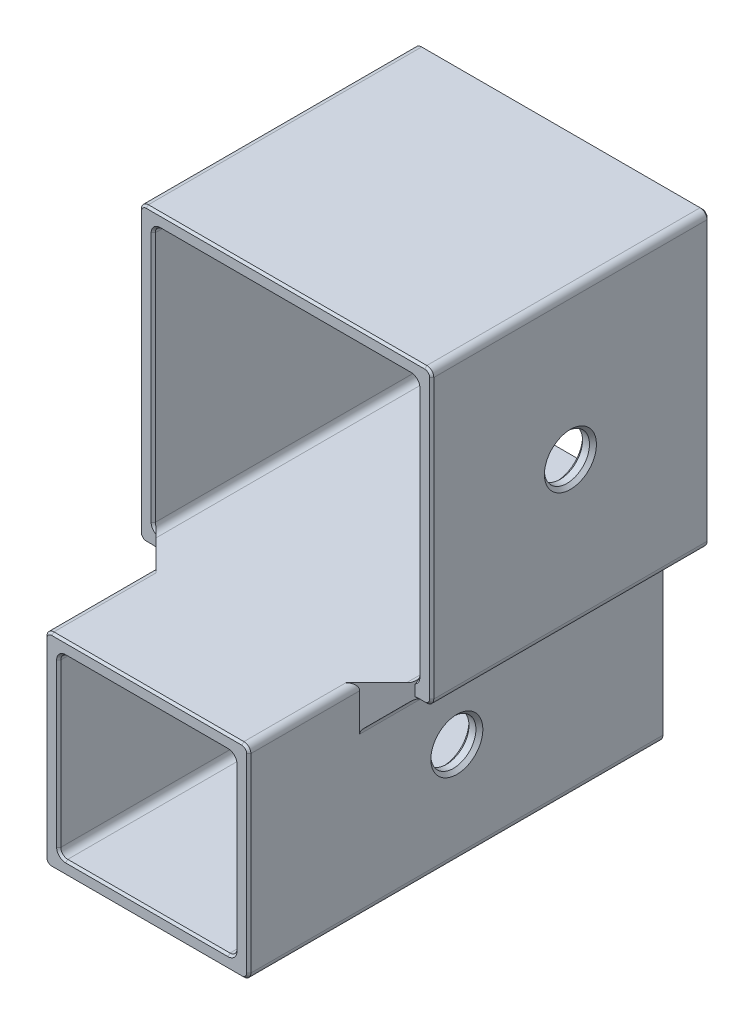
SolidWorks part; units mm, degrees
ref_plane "Front Plane" through (0, 0, 0) normal (0, 0, 1) x (1, 0, 0)
ref_plane "Top Plane" through (0, 0, 0) normal (0, 1, 0) x (1, 0, 0)
ref_plane "Right Plane" through (0, 0, 0) normal (1, 0, 0) x (0, 0, -1)
sketch "Sketch1" plane through (0, 0, 0) normal (0, 0, 1) x (1, 0, 0)
  line L0 (-21.075, -21.075) -> (-21.075, 21.075)
  line L1 (19.075, -19.075) -> (-19.075, -19.075)
  line L2 (19.075, -19.075) -> (19.075, 19.075)
  line L3 (19.075, 19.075) -> (-19.075, 19.075)
  line L4 (-19.075, -19.075) -> (-19.075, 19.075)
  line L5 (19.075, -19.075) -> (-19.075, 19.075) construction
  line L6 (19.075, 19.075) -> (-19.075, -19.075) construction
  line L7 (21.075, 21.075) -> (-21.075, 21.075)
  line L8 (21.075, -21.075) -> (21.075, 21.075)
  line L9 (21.075, -21.075) -> (-21.075, -21.075)
  point P0 (0, 0)
  dimension "D1" = 38.15
  dimension "D2" = 2
extrude "Boss-Extrude1" add sketch "Sketch1" along normal blind 40
sketch "Sketch3" plane through (0, 0, 40) normal (0, 0, 1) x (1, 0, 0)
  line L1 (12.7, -46.475) -> (-12.7, -46.475)
  line L2 (12.7, -46.475) -> (12.7, -21.075)
  line L3 (12.7, -21.075) -> (-12.7, -21.075)
  line L4 (-12.7, -46.475) -> (-12.7, -21.075)
  line L5 (12.7, -46.475) -> (-12.7, -21.075) construction
  line L6 (12.7, -21.075) -> (-12.7, -46.475) construction
  line L7 (-21.075, -21.075) -> (21.075, -21.075) construction
  line L8 (-14.7, -48.475) -> (-14.7, -19.075)
  line L9 (14.7, -19.075) -> (-14.7, -19.075)
  line L10 (14.7, -48.475) -> (14.7, -19.075)
  line L11 (14.7, -48.475) -> (-14.7, -48.475)
  point P0 (0, -33.775)
  point P7 (0, 0)
  dimension "D1" = 25.4
  dimension "D2" = 2
extrude "Boss-Extrude2" add sketch "Sketch3" along normal blind 20 and the other way up to surface
chamfer "Chamfer1" distance 4 angle 45 4 edges at (14.7, -20.075, 40) (-14.7, -20.075, 40) (14.7, -21.075, 20) (-14.7, -21.075, 20)
fillet "Fillet1" radius 1 20 edges at (-18.7, -21.075, 20) (-14.7, -25.075, 22) (14.7, -25.075, 22) (18.7, -21.075, 20) (14.7, -48.475, 30) (-14.7, -48.475, 30) (-21.075, -21.075, 20) (21.075, -21.075, 20) (21.075, 21.075, 20) (-21.075, 21.075, 20) (12.7, -46.475, 30) (12.7, -21.075, 30) (-12.7, -21.075, 30) (-12.7, -46.475, 30) (-19.075, -19.075, 20) (-19.075, 19.075, 20) (19.075, 19.075, 20) (19.075, -19.075, 20) (14.7, -19.075, 52) (-14.7, -19.075, 52)
chamfer "Chamfer2" distance 0.3 angle 45 70 edges at (-19.5946, -21.075, 40) (-16.7, -23.075, 0) (16.7, -23.075, 0) (19.5946, -21.075, 40) (19.5946, -21.075, 0) (0, -48.475, 0) (19.075, 0, 0) (0, 19.075, 0) (-19.075, 0, 0) (-21.075, 0, 0) (0, 21.075, 0) (21.075, 0, 0) (12.7, -33.775, 0) (0, -21.075, 0) (-12.7, -33.775, 0) (0, -46.475, 0) (-20.7821, 20.7821, 0) (20.7821, 20.7821, 0) (20.7821, -20.7821, 0) (-20.7821, -20.7821, 0) (-14.4071, -48.1821, 0) (14.4071, -48.1821, 0) (-21.075, 0, 40) (21.075, 0, 40) (0, 21.075, 40) (-19.075, 0, 40) (0, 19.075, 40) (19.075, 0, 40) (-20.7821, 20.7821, 40) (20.7821, 20.7821, 40) (20.7821, -20.7821, 40) (-20.7821, -20.7821, 40) (-18.9023, -21.0977, 40) (-18.7315, -21.1511, 0) (-14.7761, -25.1065, 0) (14.7761, -25.1065, 0) (18.7315, -21.1511, 0) (18.9023, -21.0977, 40) (12.4071, -46.1821, 60) (12.4071, -46.1821, 0) (12.4071, -21.3679, 60) (12.4071, -21.3679, 0) (-12.4071, -21.3679, 60) (-12.4071, -21.3679, 0) (-12.4071, -46.1821, 60) (-12.4071, -46.1821, 0) (-18.7821, -18.7821, 0) (-18.9764, -18.508, 40) (-18.7821, 18.7821, 0) (-18.7821, 18.7821, 40) (18.7821, 18.7821, 0) (18.7821, 18.7821, 40) (18.7821, -18.7821, 0) (18.9764, -18.508, 40) (14.7, -36.4821, 0) (14.7, -33.775, 60) (0, -48.475, 60) (0, -19.075, 60) (-14.7, -33.775, 60) (-12.7, -33.775, 60) (0, -21.075, 60) (12.7, -33.775, 60) (0, -46.475, 60) (-14.4071, -48.1821, 60) (14.4071, -48.1821, 60) (-14.4071, -19.3679, 60) (14.4071, -19.3679, 60) (0, -19.075, 0) (-14.7, -36.4821, 0) (-19.5946, -21.075, 0)
sketch "Sketch6" plane through (21.075, 0, 0) normal (1, 0, 0) x (0, 0, -1)
  line L0 (-39.7, -20.075) -> (-0.3, 20.075) construction
  line L1 (-39.7, 20.075) -> (-0.3, -20.075) construction
  line L2 (-59.7, -20.075) -> (-0.3, -47.475) construction
  circle A0 centre (-20, 0) radius 3.25
  circle A1 centre (-30, -33.775) radius 3.25
  point P10 (-30, -33.775)
  dimension "D1" = 6.5
extrude "Cut-Extrude1" cut sketch "Sketch6" against normal blind 20
chamfer "Chamfer3" distance 0.5 angle 45 4 edges at (12.7, -30.525, 30) (14.7, -33.775, 26.75) (21.075, 0, 16.75) (19.075, 0, 23.25)
